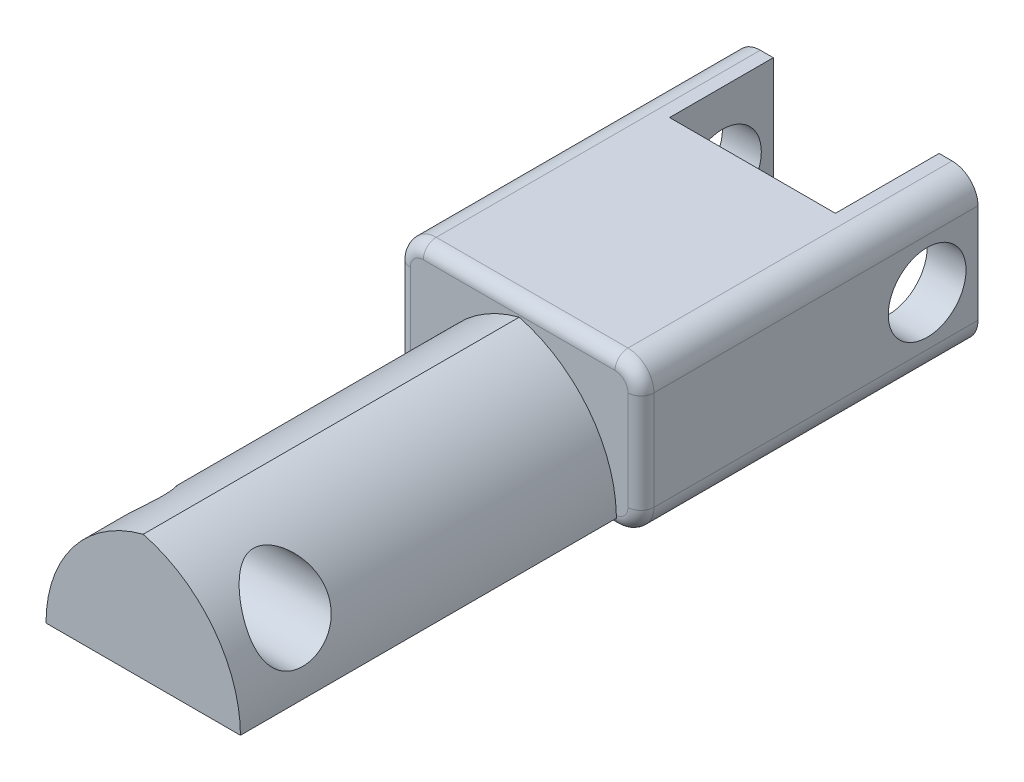
SolidWorks part; units mm, degrees
ref_plane "Front Plane" through (0, 0, 0) normal (0, 0, 1) x (1, 0, 0)
ref_plane "Top Plane" through (0, 0, 0) normal (0, 1, 0) x (1, 0, 0)
ref_plane "Right Plane" through (0, 0, 0) normal (1, 0, 0) x (0, 0, -1)
sketch "Sketch1" plane through (0, 0, 0) normal (0, 0, 1) x (1, 0, 0)
  line L1 (-7.5, 5) -> (7.5, 5)
  line L2 (-7.5, 5) -> (-7.5, -5)
  line L3 (-7.5, -5) -> (7.5, -5)
  line L4 (7.5, 5) -> (7.5, -5)
  line L5 (-7.5, 5) -> (7.5, -5) construction
  line L6 (-7.5, -5) -> (7.5, 5) construction
  point P0 (0, 0)
  dimension "D1" = 15
  dimension "D2" = 10
extrude "Boss-Extrude1" add sketch "Sketch1" along normal blind 40
sketch "Sketch2" plane through (0, 0, 40) normal (0, 0, 1) x (1, 0, 0)
  circle A0 centre (0, -1.522) radius 3.478
sketch "Sketch3" plane through (0, 0, 0) normal (0, 0, -1) x (-1, 0, 0)
  line L1 (-9.3959, 5.8234) -> (9.3959, 5.8234)
  line L2 (-9.3959, 5.8234) -> (-9.3959, -5.8234)
  line L3 (-9.3959, -5.8234) -> (9.3959, -5.8234)
  line L4 (9.3959, 5.8234) -> (9.3959, -5.8234)
  line L5 (-9.3959, 5.8234) -> (9.3959, -5.8234) construction
  line L6 (-9.3959, -5.8234) -> (9.3959, 5.8234) construction
  point P0 (0, 0)
extrude "Boss-Extrude2" add sketch "Sketch3" against normal blind 11 and the other way blind 15
sketch "Sketch4" plane through (0, 5.8234, 0) normal (0, 1, 0) x (1, 0, 0)
  line L0 (9.3959, 15) -> (-9.3959, 15) construction
  line L1 (-6.3959, 15) -> (6.3959, 15)
  line L2 (-6.3959, 15) -> (-6.3959, 7)
  line L3 (-6.3959, 7) -> (6.3959, 7)
  line L4 (6.3959, 15) -> (6.3959, 7)
  line L5 (-9.3959, 15) -> (-9.3959, -11) construction
  line L6 (9.3959, 15) -> (9.3959, -11) construction
  line L7 (-6.3959, 15) -> (6.3959, 15)
  line M6 (9.3959, 15) -> (-9.3959, 15)
  dimension "D1" = 3
  dimension "D2" = 8
  dimension "D3" = 3
extrude "Cut-Extrude1" cut sketch "Sketch4" against normal through all contours L4 L2 L3 M6 region at (0, 5.8234, -11)
sketch "Sketch5" plane through (-7.5, 0, 0) normal (-1, 0, 0) x (0, 0, 1)
  line L0 (40, -5) -> (40, 1.9561) construction
  circle A0 centre (35, 0) radius 3
  dimension "D1" = 6
  dimension "D2" = 5
extrude "Cut-Extrude2" cut sketch "Sketch5" against normal through all
sketch "Sketch6" plane through (0, 0, -7) normal (0, 0, -1) x (-1, 0, 0)
  line L1 (-7.3959, 5.8234) -> (7.3959, 5.8234)
  line L2 (-9.3959, 3.8234) -> (-9.3959, -3.8234)
  line L3 (-7.3959, -5.8234) -> (7.3959, -5.8234)
  line L4 (9.3959, 3.8234) -> (9.3959, -3.8234)
  line L5 (-9.3959, 5.8234) -> (9.3959, -5.8234) construction
  line L6 (-9.3959, -5.8234) -> (9.3959, 5.8234) construction
  arc A0 (9.3959, 3.8234) -> (7.3959, 5.8234) centre (7.3959, 3.8234) ccw
  arc A1 (9.3959, -3.8234) -> (7.3959, -5.8234) centre (7.3959, -3.8234) cw
  arc A2 (-7.3959, -5.8234) -> (-9.3959, -3.8234) centre (-7.3959, -3.8234) cw
  arc A3 (-9.3959, 3.8234) -> (-7.3959, 5.8234) centre (-7.3959, 3.8234) cw
  point P0 (0, 0)
  dimension "D1" = 2
extrude "Cut-Extrude3" cut sketch "Sketch6" against normal through all and the other way through all flip side to cut
fillet "Fillet1" radius 10 2 edges at (-7.5, 5, 25.5) (7.5, 5, 25.5)
fillet "Fillet2" radius 1 7 edges at (-8.8101, 5.2376, 11) (-9.3959, 0, 11) (-8.8101, -5.2376, 11) (8.8101, -5.2376, 11) (9.3959, 0, 11) (8.8101, 5.2376, 11) (0, 5.8234, 11)
sketch "Sketch7" plane through (9.3959, 0, 0) normal (1, 0, 0) x (0, 0, -1)
  circle A0 centre (11.0767, 0) radius 3
  point P2 (11.0767, 0)
  dimension "D1" = 6
extrude "Cut-Extrude4" cut sketch "Sketch7" against normal through all contours A0
